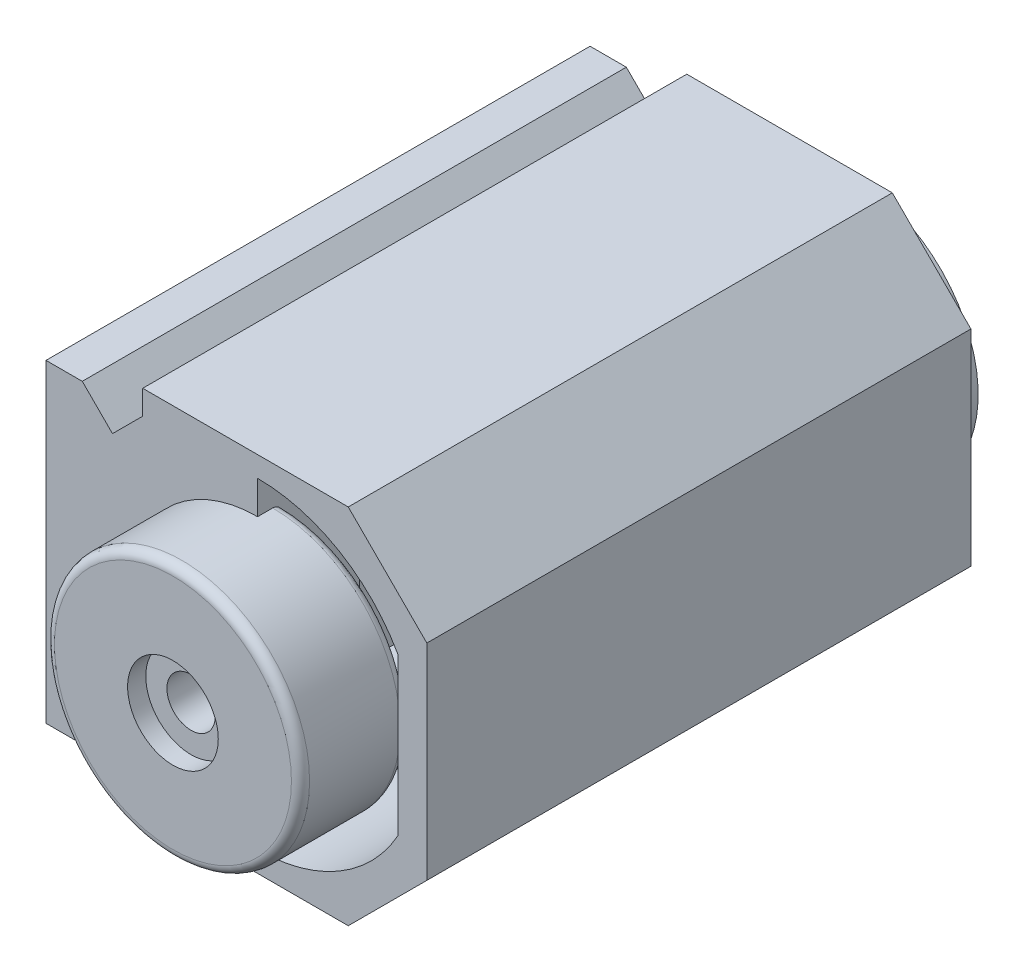
SolidWorks part; units mm, degrees
material "PLA"
ref_plane "Front Plane" through (0, 0, 0) normal (0, 0, 1) x (1, 0, 0)
ref_plane "Top Plane" through (0, 0, 0) normal (0, 1, 0) x (1, 0, 0)
ref_plane "Right Plane" through (0, 0, 0) normal (1, 0, 0) x (0, 0, -1)
sketch "Sketch1" plane through (0, 0, 0) normal (0, 0, 1) x (1, 0, 0)
  line L0 (8.5, 15) -> (16, 7.5)
  line L1 (-8.5, -15) -> (8.5, -15)
  line L2 (-8.5, -15) -> (-8.5, -13)
  line L3 (-8.5, 15) -> (8.5, 15)
  line L4 (16, -7.5) -> (16, 7.5)
  line L5 (-8.5, -13) -> (-11, -10.5)
  line L6 (-11, -10.5) -> (-13.5, -13)
  line L7 (16, -7.5) -> (8.5, -15)
  line L8 (-13.5, -13) -> (-16.5, -13)
  line L9 (-16.5, -13) -> (-16.5, 13)
  line L10 (-20.0413, 0) -> (-5.6628, 0) construction
  line L11 (-8.5, 13) -> (-11, 10.5)
  line L12 (-11, 10.5) -> (-13.5, 13)
  line L13 (-13.5, 13) -> (-16.5, 13)
  line L14 (-8.5, 13) -> (-8.5, 15)
  point P0 (0, 0)
  point P10 (0, 15)
  point P21 (-16.5, 0)
  dimension "D6" = 2
  dimension "D1" = 24.5
  dimension "D2" = 30
  dimension "D3" = 45
  dimension "D4" = 45
  dimension "D5" = 15
  dimension "D7" = 2.5
  dimension "D8" = 2.5
  dimension "D9" = 3
  dimension "D10" = 2
extrude "Boss-Extrude1" add sketch "Sketch1" along normal mid plane 45
sketch "Sketch2" plane through (0, 0, -22.5) normal (0, 0, -1) x (-1, 0, 0)
  line L0 (16.5, 13) -> (16.5, -13) construction
  circle A0 centre (-1, 0) radius 10.5
  circle A1 centre (-1, 0) radius 2
  circle A2 centre (-1, 6) radius 0.5
  circle A3 centre (-1, -6) radius 0.5
  dimension "D1" = 21
  dimension "D3" = 4
  dimension "D4" = 1
  dimension "D6" = 1
  dimension "D2" = 17.5
  dimension "D5" = 6
  dimension "D7" = 6
extrude "Boss-Extrude2" add sketch "Sketch2" along normal blind 4.1
sketch "Sketch4" plane through (0, 0, 22.5) normal (0, 0, 1) x (1, 0, 0)
  line L0 (-16.5, 13) -> (-16.5, -13) construction
  circle A0 centre (1, 0) radius 10.55
  circle A1 centre (1, 0) radius 2
  dimension "D1" = 21.1
  dimension "D3" = 4
  dimension "D2" = 17.5
extrude "Boss-Extrude3" add sketch "Sketch4" along normal blind 7
sketch "Sketch5" plane through (0, 0, 29.5) normal (0, 0, 1) x (1, 0, 0)
  circle A0 centre (1, 0) radius 3.75
  dimension "D1" = 7.5
extrude "Cut-Extrude1" cut sketch "Sketch5" against normal blind 1.5
sketch "Sketch6" plane through (0, 0, 22.5) normal (0, 0, 1) x (1, 0, 0)
  line L0 (1, 13.3) -> (1, 10.55)
  line L1 (1, -10.55) -> (1, -13.3)
  arc A0 (1, -13.3) -> (1, 13.3) centre (1, 0) ccw
  circle A1 centre (1, 0) radius 10.55 construction
  arc A2 (1, -10.55) -> (1, 10.55) centre (1, 0) ccw
  dimension "D1" = 2.75
extrude "Cut-Extrude2" cut sketch "Sketch6" against normal blind 15
sketch "Sketch8" plane through (-16.5, 0, 0) normal (-1, 0, 0) x (0, 0, 1)
  line L0 (-22.5, 13) -> (-22.5, -13) construction
  line L1 (-21, 6.5) -> (12, 6.5)
  line L2 (-21, 6.5) -> (-21, -6.5)
  line L3 (-21, -6.5) -> (12, -6.5)
  line L4 (12, 6.5) -> (12, -6.5)
  line L5 (22.5, -13) -> (-22.5, -13) construction
  line L6 (22.5, 13) -> (22.5, -13) construction
  point P6 (-21, 0)
  dimension "D1" = 1.5
  dimension "D2" = 6.5
  dimension "D3" = 10.5
extrude "Cut-Extrude4" cut sketch "Sketch8" against normal blind 11.75
sketch "Sketch9" plane through (-4.75, 0, 0) normal (-1, 0, 0) x (0, 0, 1)
  line L0 (12, 6.5) -> (-21, 6.5) construction
  line L1 (-15.85, 6.5) -> (7.05, 6.5)
  line L2 (-15.85, 6.5) -> (-15.85, -6.5)
  line L3 (-15.85, -6.5) -> (7.05, -6.5)
  line L4 (7.05, 6.5) -> (7.05, -6.5)
  line L5 (-21, -6.5) -> (12, -6.5) construction
  line L6 (-21, 6.5) -> (-21, -6.5) construction
  dimension "D1" = 22.9
  dimension "D2" = 5.15
extrude "Cut-Extrude5" cut sketch "Sketch9" against normal blind 17
sketch "Sketch10" plane through (-16.5, 0, 0) normal (-1, 0, 0) x (0, 0, 1)
  line L0 (7.05, 6.5) -> (-15.85, 6.5) construction
  line L1 (-15.85, -6.5) -> (7.05, -6.5) construction
  circle A0 centre (0, 9) radius 0.75
  circle A1 centre (0, -9) radius 0.75
  dimension "D1" = 1.5
  dimension "D3" = 1.5
  dimension "D2" = 2.5
  dimension "D4" = 2.5
extrude "Cut-Extrude6" cut sketch "Sketch10" against normal blind 8
sketch "Sketch11" plane through (-4.75, 0, 0) normal (-1, 0, 0) x (0, 0, 1)
  line L1 (7.05, -6.5) -> (7.05, 6.5) construction
  circle A0 centre (-19.05, 0) radius 0.9
  circle A1 centre (8.75, 0) radius 0.9
  dimension "D1" = 1.8
  dimension "D3" = 1.8
  dimension "D2" = 27.8
  dimension "D4" = 1.7
extrude "Cut-Extrude7" cut sketch "Sketch11" against normal blind 10.75
ref_plane "Plane1" through (0, 0, 20.5) normal (0, 0, 1) x (1, 0, 0)
sketch "Sketch12" plane through (0, 0, 20.5) normal (0, 0, 1) x (1, 0, 0)
  line L0 (1, 13.3) -> (1, -13.3)
  arc A0 (1, -13.3) -> (1, 13.3) centre (1, 0) ccw construction
  arc A1 (1, -13.3) -> (1, 13.3) centre (1, 0) ccw
extrude "Cut-Extrude8" cut sketch "Sketch12" against normal blind 13
fillet "Fillet2" radius 0.75 2 edges at (11.55, 0, 20.5) (11.55, 0, 29.5)
sketch "Sketch14" plane through (0, 0, 7.05) normal (0, 0, -1) x (-1, 0, 0)
  line L1 (-12.25, 6.5) -> (1.25, 6.5)
  line L2 (-12.25, 6.5) -> (-12.25, -6.5)
  line L3 (-12.25, -6.5) -> (1.25, -6.5)
  line L4 (1.25, 6.5) -> (1.25, -6.5)
  line L5 (-12.25, 6.5) -> (4.75, 6.5) construction
  line L6 (-12.25, -6.5) -> (-12.25, 6.5) construction
  line L7 (-12.25, -6.5) -> (4.75, -6.5) construction
  dimension "D1" = 13.5
extrude "Cut-Extrude9" cut sketch "Sketch14" against normal blind 7
fillet "Fillet3" radius 6 2 edges at (6.625, -6.5, 7.5) (6.625, 6.5, 7.5)
sketch "Sketch15" plane through (0, 0, 22.5) normal (0, 0, 1) x (1, 0, 0)
  line L0 (16, -7.5) -> (16, 7.5) construction
  line L1 (17, -10.2213) -> (15, -10.2213)
  line L2 (17, -10.2213) -> (17, 10.2213)
  line L3 (17, 10.2213) -> (15, 10.2213)
  line L4 (15, -10.2213) -> (15, 10.2213)
  line L5 (17, -10.2213) -> (15, 10.2213) construction
  line L6 (17, 10.2213) -> (15, -10.2213) construction
  point P0 (16, 0)
  dimension "D1" = 2
extrude "Cut-Extrude10" cut sketch "Sketch15" against normal through all
sketch "Sketch16" plane through (0, 0, 22.5) normal (0, 0, 1) x (1, 0, 0)
  line L0 (15, 8.5) -> (15, -8.5) construction
  line L1 (12.6034, 6.5) -> (15, 6.5)
  line L2 (12.6034, 6.5) -> (12.6034, -6.5)
  line L3 (12.6034, -6.5) -> (15, -6.5)
  line L4 (15, 6.5) -> (15, -6.5)
  line L5 (12.25, -6.5) -> (-4.75, -6.5) construction
  line L6 (12.25, 6.5) -> (-4.75, 6.5) construction
  arc A0 (1, -13.3) -> (1, 13.3) centre (1, 0) ccw construction
extrude "Boss-Extrude5" add sketch "Sketch16" against normal up to surface (15 mm away) up to face at (2.526, -12.8328, 7.5)
chamfer "Chamfer1" distance 0.35 distance2 1 1 edges at (12.25, 0, 7.5) first distance on face at (12.4287, 0, 7.5)
sketch "Sketch17" plane through (-16.5, 0, 0) normal (-1, 0, 0) x (0, 0, 1)
  line L1 (-21, 6.5) -> (-21.25, 6.5)
  line L2 (-21, 6.5) -> (-21, -6.5)
  line L3 (-21, -6.5) -> (-21.25, -6.5)
  line L4 (-21.25, 6.5) -> (-21.25, -6.5)
  dimension "D1" = 0.25
extrude "Cut-Extrude11" cut sketch "Sketch17" against normal up to surface (11.75 mm away) up to face at (-4.75, 0, -18.15)
